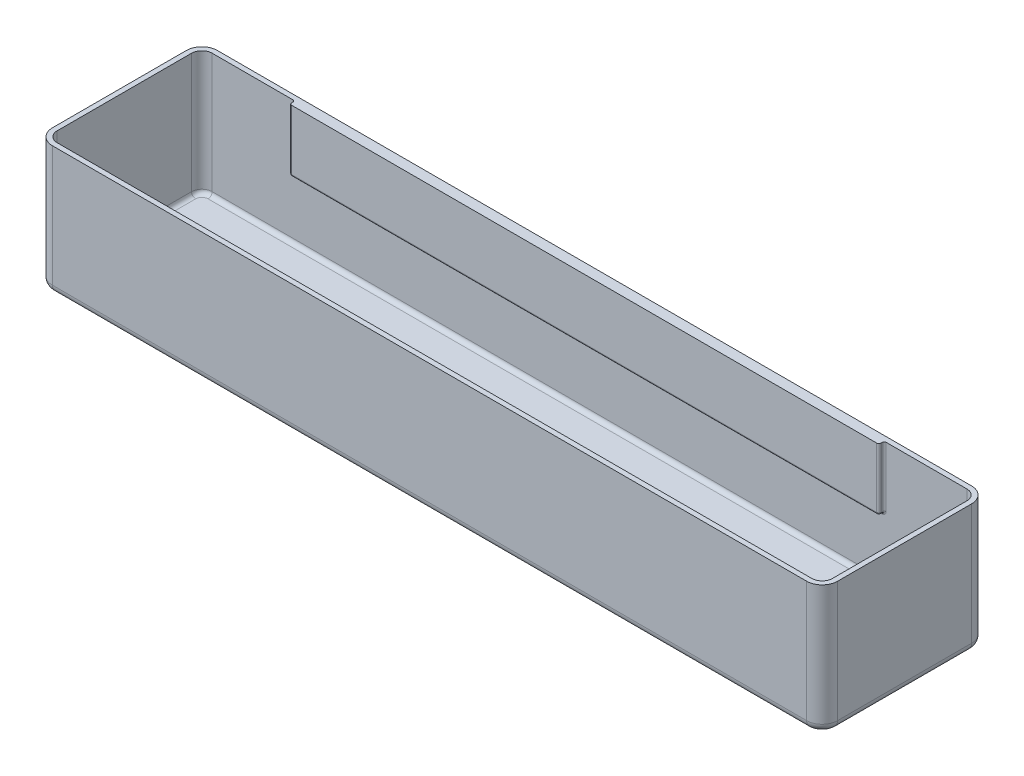
SolidWorks part; units mm, degrees
material "NEOPRENE"
ref_plane "Front" through (0, 0, 0) normal (0, 0, 1) x (1, 0, 0)
ref_plane "Top" through (0, 0, 0) normal (0, 1, 0) x (1, 0, 0)
ref_plane "Right" through (0, 0, 0) normal (1, 0, 0) x (0, 0, -1)
sketch "Sketch1" plane through (0, 0, 0) normal (0, 1, 0) x (1, 0, 0)
  line L0 (-119.0625, 0) -> (-120.5865, 0) construction
  line L1 (-120.5865, 25.3365) -> (120.5865, 25.3365)
  line L2 (-120.5865, 25.3365) -> (-120.5865, -25.3365)
  line L3 (-120.5865, -25.3365) -> (120.5865, -25.3365)
  line L4 (120.5865, 25.3365) -> (120.5865, -25.3365)
  line L5 (-120.5865, 25.3365) -> (120.5865, -25.3365) construction
  line L6 (-120.5865, -25.3365) -> (120.5865, 25.3365) construction
  line L7 (119.0625, 23.8125) -> (-119.0625, 23.8125)
  line L8 (119.0625, 23.8125) -> (119.0625, -23.8125)
  line L9 (119.0625, -23.8125) -> (-119.0625, -23.8125)
  line L10 (-119.0625, 23.8125) -> (-119.0625, -23.8125)
  line L11 (119.0625, 23.8125) -> (-119.0625, -23.8125) construction
  line L12 (119.0625, -23.8125) -> (-119.0625, 23.8125) construction
  line L13 (0, 23.8125) -> (0, 25.3365) construction
  point P0 (0, 0)
  point P6 (0, 0)
  dimension "D1" = 238.125
  dimension "D2" = 47.625
  dimension "THICKNESS" = 1.524
extrude "Boss-Extrude1" add sketch "Sketch1" along normal blind 38.1
sketch "Sketch2" plane through (0, 0, 0) normal (0, -1, 0) x (1, 0, 0)
  line L4 (120.5865, -25.3365) -> (120.5865, 25.3365)
  line L5 (120.5865, 25.3365) -> (-120.5865, 25.3365)
  line L6 (-120.5865, 25.3365) -> (-120.5865, -25.3365)
  line L7 (-120.5865, -25.3365) -> (120.5865, -25.3365)
  line L8 (120.5865, -25.3365) -> (120.5865, 25.3365)
  line L9 (120.5865, 25.3365) -> (-120.5865, 25.3365)
  line L10 (-120.5865, 25.3365) -> (-120.5865, -25.3365)
  line L11 (-120.5865, -25.3365) -> (120.5865, -25.3365)
  arc A0 (104.4707, 2.6288) -> (104.0355, 6.8062) centre (104.2531, 4.7175) ccw construction
  arc A1 (104.0355, 6.8062) -> (104.4707, 2.6288) centre (104.2531, 4.7175) ccw construction
  arc A2 (73.6375, -0.5832) -> (73.2023, 3.5942) centre (73.4199, 1.5055) ccw construction
  arc A3 (73.2023, 3.5942) -> (73.6375, -0.5832) centre (73.4199, 1.5055) ccw construction
  arc A4 (104.4707, 2.6288) -> (104.0355, 6.8062) centre (104.2531, 4.7175) ccw
  arc A5 (104.0355, 6.8062) -> (104.4707, 2.6288) centre (104.2531, 4.7175) ccw
  arc A6 (73.6375, -0.5832) -> (73.2023, 3.5942) centre (73.4199, 1.5055) ccw
  arc A7 (73.2023, 3.5942) -> (73.6375, -0.5832) centre (73.4199, 1.5055) ccw
  dimension "D1" = 0
extrude "Boss-Extrude2" add sketch "Sketch2" along normal blind 1.524
fillet "Fillet1" radius 3.175 4 edges at (119.0625, 19.05, -23.8125) (119.0625, 19.05, 23.8125) (-119.0625, 19.05, 23.8125) (-119.0625, 19.05, -23.8125)
fillet "Fillet2" radius 4.7625 4 edges at (-120.5865, 18.288, -25.3365) (120.5865, 18.288, -25.3365) (120.5865, 18.288, 25.3365) (-120.5865, 18.288, 25.3365)
sketch "Sketch4" plane through (0, -1.524, 0) normal (0, -1, 0) x (1, 0, 0)
  line L2 (120.5865, -20.574) -> (120.5865, 20.574) construction
  line L3 (115.824, 25.3365) -> (-115.824, 25.3365) construction
  circle A0 centre (88.8365, 3.1115) radius 12.065
  dimension "D1" = 24.13
  dimension "D3" = 22.225
  dimension "D2" = 31.75
extrude "Cut-Extrude2" cut sketch "Sketch4" against normal through all
sketch "Sketch5" plane through (0, 0, -23.8125) normal (0, 0, 1) x (1, 0, 0)
  line L0 (0, 0) -> (0, 28.575) construction
  line L1 (115.8875, 38.1) -> (-115.8875, 38.1) construction
  line L2 (-90.4875, 19.05) -> (90.4875, 19.05)
  line L3 (-90.4875, 19.05) -> (-90.4875, 38.1)
  line L4 (-90.4875, 38.1) -> (90.4875, 38.1)
  line L5 (90.4875, 19.05) -> (90.4875, 38.1)
  line L6 (-90.4875, 19.05) -> (90.4875, 38.1) construction
  line L7 (-90.4875, 38.1) -> (90.4875, 19.05) construction
  dimension "D1" = 180.975
  dimension "D2" = 19.05
extrude "Boss-Extrude3" add sketch "Sketch5" along normal blind 1.651
fillet "Fillet3" radius 0.635 8 edges at (0, 19.05, -22.1615) (0, 19.05, -23.8125) (-90.4875, 28.575, -23.8125) (-90.4875, 28.575, -22.1615) (90.4875, 28.575, -22.1615) (90.4875, 28.575, -23.8125) (-90.4875, 19.05, -22.987) (90.4875, 19.05, -22.987)
fillet "Fillet4" radius 1.27 8 edges at (118.1326, 0, -22.8826) (119.0625, 0, 0) (118.1326, 0, 22.8826) (0, 0, 23.8125) (-118.1326, 0, 22.8826) (-119.0625, 0, 0) (-118.1326, 0, -22.8826) (0, 0, -23.8125)
fillet "Fillet5" radius 2.54 8 edges at (-119.1916, -1.524, 23.9416) (0, -1.524, 25.3365) (119.1916, -1.524, 23.9416) (120.5865, -1.524, 0) (119.1916, -1.524, -23.9416) (0, -1.524, -25.3365) (-119.1916, -1.524, -23.9416) (-120.5865, -1.524, 0)
sketch "Sketch6" [suppressed] plane through (0, -1.524, 0) normal (0, -1, 0) x (1, 0, 0)
  circle A0 centre (73.3365, 3.1115) radius 2.1 construction
  circle A1 centre (73.3365, 3.1115) radius 2.1
  circle A2 centre (104.3365, 3.1115) radius 2.1 construction
  circle A3 centre (104.3365, 3.1115) radius 2.1
extrude "Boss-Extrude4" [suppressed] add sketch "Sketch6" against normal up to surface (1.524 mm away) up to face at (0, 0, 0)
sketch "Sketch7" [suppressed] plane through (0, -1.524, 0) normal (0, -1, 0) x (1, 0, 0)
  circle A0 centre (-45.2, 0.936) radius 12.192
  circle A1 centre (45, 0.936) radius 12.192
  dimension "D1" = 24.384
extrude "Cut-Extrude3" [suppressed] cut sketch "Sketch7" against normal through all
sketch "Sketch8" [suppressed] plane through (0, 38.1, 0) normal (0, 1, 0) x (1, 0, 0)
  line L0 (-90.4875, 22.5425) -> (-90.4875, 23.1775) construction
  line L1 (89.8525, 21.9075) -> (-89.8525, 21.9075) construction
  line L2 (90.4875, 22.5425) -> (90.4875, 23.1775) construction
  line L3 (115.8875, 23.8125) -> (91.1225, 23.8125) construction
  line L4 (115.824, 25.3365) -> (-115.824, 25.3365)
  line L5 (-120.5865, 20.574) -> (-120.5865, -20.574)
  line L6 (-115.824, -25.3365) -> (115.824, -25.3365)
  line L7 (120.5865, -20.574) -> (120.5865, 20.574)
  line L8 (115.824, 25.3365) -> (-115.824, 25.3365)
  line L9 (-120.5865, 20.574) -> (-120.5865, -20.574)
  line L10 (-115.824, -25.3365) -> (115.824, -25.3365)
  line L11 (120.5865, -20.574) -> (120.5865, 20.574)
  line L12 (119.0625, -20.6375) -> (119.0625, 20.6375) construction
  line L13 (-115.8875, -23.8125) -> (115.8875, -23.8125) construction
  line L14 (-91.1225, 23.8125) -> (-115.8875, 23.8125) construction
  line L15 (-119.0625, 20.6375) -> (-119.0625, -20.6375) construction
  line L16 (-90.4875, 22.5425) -> (-90.4875, 23.1775)
  line L17 (89.8525, 21.9075) -> (-89.8525, 21.9075)
  line L18 (90.4875, 22.5425) -> (90.4875, 23.1775)
  line L19 (115.8875, 23.8125) -> (91.1225, 23.8125)
  line L20 (119.0625, -20.6375) -> (119.0625, 20.6375)
  line L21 (-115.8875, -23.8125) -> (115.8875, -23.8125)
  line L22 (-91.1225, 23.8125) -> (-115.8875, 23.8125)
  line L23 (-119.0625, 20.6375) -> (-119.0625, -20.6375)
  arc A0 (-90.4875, 23.1775) -> (-91.1225, 23.8125) centre (-91.1225, 23.1775) ccw construction
  arc A1 (-90.4875, 22.5425) -> (-89.8525, 21.9075) centre (-89.8525, 22.5425) ccw construction
  arc A2 (89.8525, 21.9075) -> (90.4875, 22.5425) centre (89.8525, 22.5425) ccw construction
  arc A3 (91.1225, 23.8125) -> (90.4875, 23.1775) centre (91.1225, 23.1775) ccw construction
  arc A4 (-115.824, 25.3365) -> (-120.5865, 20.574) centre (-115.824, 20.574) ccw
  arc A5 (-120.5865, -20.574) -> (-115.824, -25.3365) centre (-115.824, -20.574) ccw
  arc A6 (115.824, -25.3365) -> (120.5865, -20.574) centre (115.824, -20.574) ccw
  arc A7 (120.5865, 20.574) -> (115.824, 25.3365) centre (115.824, 20.574) ccw
  arc A8 (-115.824, 25.3365) -> (-120.5865, 20.574) centre (-115.824, 20.574) ccw
  arc A9 (-120.5865, -20.574) -> (-115.824, -25.3365) centre (-115.824, -20.574) ccw
  arc A10 (115.824, -25.3365) -> (120.5865, -20.574) centre (115.824, -20.574) ccw
  arc A11 (120.5865, 20.574) -> (115.824, 25.3365) centre (115.824, 20.574) ccw
  arc A12 (119.0625, 20.6375) -> (115.8875, 23.8125) centre (115.8875, 20.6375) ccw construction
  arc A13 (115.8875, -23.8125) -> (119.0625, -20.6375) centre (115.8875, -20.6375) ccw construction
  arc A14 (-115.8875, 23.8125) -> (-119.0625, 20.6375) centre (-115.8875, 20.6375) ccw construction
  arc A15 (-119.0625, -20.6375) -> (-115.8875, -23.8125) centre (-115.8875, -20.6375) ccw construction
  arc A16 (-90.4875, 23.1775) -> (-91.1225, 23.8125) centre (-91.1225, 23.1775) ccw
  arc A17 (-90.4875, 22.5425) -> (-89.8525, 21.9075) centre (-89.8525, 22.5425) ccw
  arc A18 (89.8525, 21.9075) -> (90.4875, 22.5425) centre (89.8525, 22.5425) ccw
  arc A19 (91.1225, 23.8125) -> (90.4875, 23.1775) centre (91.1225, 23.1775) ccw
  arc A20 (119.0625, 20.6375) -> (115.8875, 23.8125) centre (115.8875, 20.6375) ccw
  arc A21 (115.8875, -23.8125) -> (119.0625, -20.6375) centre (115.8875, -20.6375) ccw
  arc A22 (-115.8875, 23.8125) -> (-119.0625, 20.6375) centre (-115.8875, 20.6375) ccw
  arc A23 (-119.0625, -20.6375) -> (-115.8875, -23.8125) centre (-115.8875, -20.6375) ccw
  dimension "D1" = 0
extrude "Cut-Extrude4" [suppressed] cut sketch "Sketch8" against normal blind 9.525
equation "\"D1@Boss-Extrude2\"=\"THICKNESS\""
